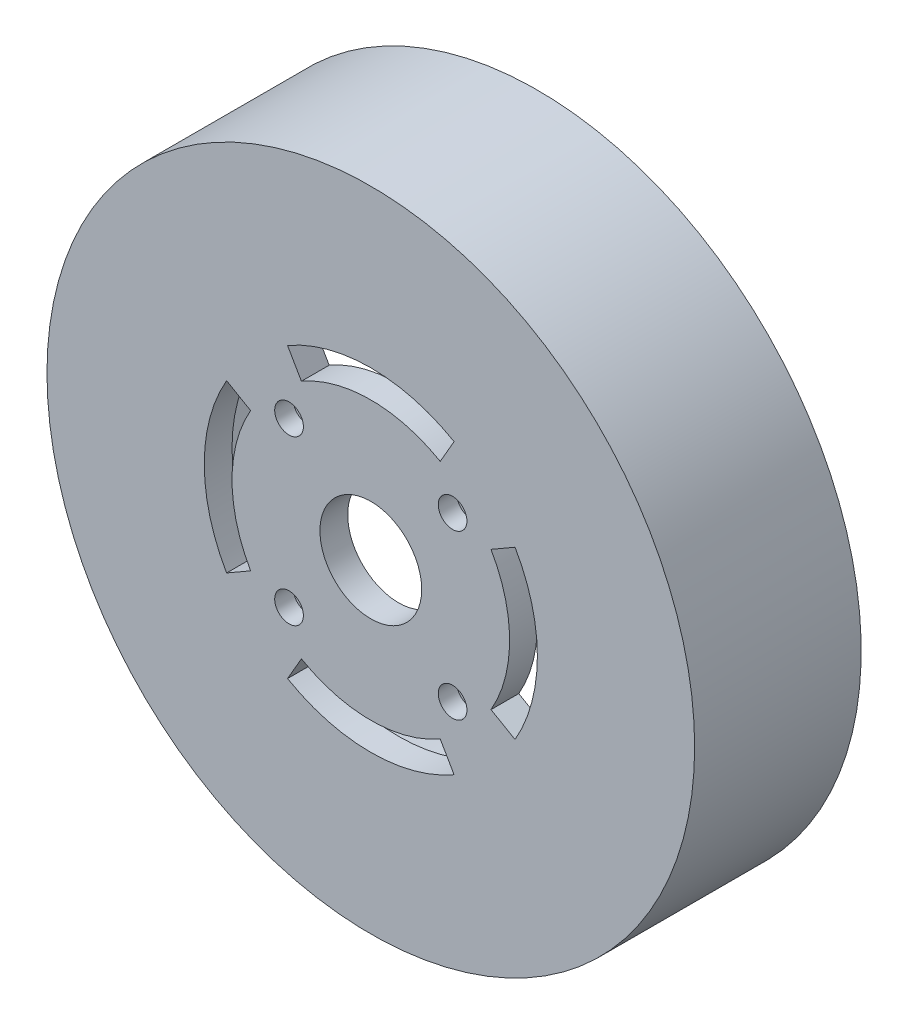
SolidWorks part; units mm, degrees
ref_plane "前视基准面" through (0, 0, 0) normal (0, 0, 1) x (1, 0, 0)
ref_plane "上视基准面" through (0, 0, 0) normal (0, 1, 0) x (1, 0, 0)
ref_plane "右视基准面" through (0, 0, 0) normal (1, 0, 0) x (0, 0, -1)
other "Configuration Table"
sketch "草图2" plane through (0, 0, 0) normal (0, 0, 1) x (1, 0, 0)
  circle A0 centre (0, 0) radius 35
  circle A1 centre (0, 0) radius 5.5
  dimension "D1" = 70
  dimension "D2" = 11
extrude "凸台-拉伸1" add sketch "草图2" along normal blind 5
sketch "草图3" plane through (0, 0, 0) normal (0, 0, -1) x (-1, 0, 0)
  circle A0 centre (0, 0) radius 30.1
  circle A1 centre (0, 0) radius 35
  dimension "D1" = 60.2
extrude "凸台-拉伸2" add sketch "草图3" along normal blind 15
sketch "草图4" plane through (0, 0, -15) normal (0, 0, -1) x (-1, 0, 0)
  line L0 (0, 0) -> (0, 32.5)
  line L1 (0, 0) -> (32.5, 0)
  line L2 (0, 0) -> (0, -32.5)
  line L3 (0, 0) -> (-32.5, 0)
  circle A0 centre (0, 32.5) radius 1.55
  circle A1 centre (32.5, 0) radius 1.55
  circle A2 centre (0, -32.5) radius 1.55
  circle A3 centre (-32.5, 0) radius 1.55
  point P9 (0, 0)
  point P17 (0, 0)
  dimension "D2" = 4
  dimension "D1" = 4
extrude "切除-拉伸1" cut sketch "草图4" against normal blind 10 contours A0 | A1 | A2 | A3 region at (1.065, 33.565, -15) region at (-32.5, 1.5062, -15) region at (-1.065, -31.435, -15) region at (34.0062, 0, -15)
sketch "草图9" plane through (0, 0, -15) normal (0, 0, -1) x (-1, 0, 0)
  line L0 (0, 0) -> (0, 32.5) construction
  line L1 (0, 0) -> (-21.2839, 21.2839) construction
  circle A0 centre (0, 0) radius 30.1 construction
  arc A1 (-22.0133, 20.5286) -> (-20.5286, 22.0133) centre (-21.2839, 21.2839) cw
  arc A2 (20.5286, 22.0133) -> (22.0133, 20.5286) centre (21.2839, 21.2839) cw
  arc A3 (22.0133, -20.5286) -> (20.5286, -22.0133) centre (21.2839, -21.2839) cw
  arc A4 (-20.5286, -22.0133) -> (-22.0133, -20.5286) centre (-21.2839, -21.2839) cw
  arc A5 (-20.5286, 22.0133) -> (-22.0133, 20.5286) centre (0, 0) ccw
  arc A6 (-22.0133, -20.5286) -> (-20.5286, -22.0133) centre (0, 0) ccw
  arc A7 (20.5286, -22.0133) -> (22.0133, -20.5286) centre (0, 0) ccw
  arc A8 (22.0133, 20.5286) -> (20.5286, 22.0133) centre (0, 0) ccw
  point P21 (0, 0)
  dimension "D2" = 1.05
  dimension "D1" = 45
  dimension "D3" = 4
extrude "切除-拉伸5" cut sketch "草图9" against normal up to surface (15 mm away) up to face at (5.5, 0, 0)
fillet "圆角1" radius 1 4 edges at (0, -30.1, -15) (-30.1, 0, -15) (0, 30.1, -15) (30.1, 0, -15)
sketch "草图10" plane through (0, 0, 5) normal (0, 0, 1) x (1, 0, 0)
  circle A0 centre (0, 0) radius 35
extrude "切除-拉伸6" cut sketch "草图10" against normal blind 2
sketch "草图11" plane through (0, 0, 0) normal (0, 0, -1) x (-1, 0, 0)
  line L0 (0, 0) -> (0, 32.5) construction
  line L1 (0, 0) -> (32.5, 0) construction
  line L2 (12.9904, 7.5) -> (15.5885, 9)
  line L3 (-7.5, 12.9904) -> (-9, 15.5885)
  line L4 (7.5, 12.9904) -> (9, 15.5885)
  line L5 (12.9904, -7.5) -> (15.5885, -9)
  line L6 (0, 0) -> (0, -32.5) construction
  line L7 (7.5, -12.9904) -> (9, -15.5885)
  line L8 (-7.5, -12.9904) -> (-9, -15.5885)
  line L9 (0, 0) -> (-32.5, 0) construction
  line L10 (-12.9904, -7.5) -> (-15.5885, -9)
  line L11 (-12.9904, 7.5) -> (-15.5885, 9)
  arc A1 (7.5, 12.9904) -> (-7.5, 12.9904) centre (0, 0) ccw
  arc A2 (9, 15.5885) -> (-9, 15.5885) centre (0, 0) ccw
  arc A3 (12.9904, -7.5) -> (12.9904, 7.5) centre (0, 0) ccw
  arc A4 (15.5885, -9) -> (15.5885, 9) centre (0, 0) ccw
  arc A5 (-7.5, -12.9904) -> (7.5, -12.9904) centre (0, 0) ccw
  arc A6 (-9, -15.5885) -> (9, -15.5885) centre (0, 0) ccw
  arc A7 (-12.9904, 7.5) -> (-12.9904, -7.5) centre (0, 0) ccw
  arc A8 (-15.5885, 9) -> (-15.5885, -9) centre (0, 0) ccw
  point P26 (0, 0)
  dimension "D4" = 30
  dimension "D1" = 4
extrude "切除-拉伸7" cut sketch "草图11" against normal blind 10
sketch "Sketch5" plane through (0, 0, 3) normal (0, 0, 1) x (1, 0, 0)
  line L0 (0, 0) -> (0, 35) construction
  line L1 (0, 0) -> (-24.7487, 24.7487) construction
  line L2 (0, 0) -> (24.7487, 24.7487) construction
  line L3 (0, 0) -> (-8.8388, 8.8388) construction
  line L4 (0, 0) -> (8.8388, -8.8388) construction
  line L5 (0, 0) -> (8.8388, 8.8388) construction
  line L6 (0, 0) -> (-8.8388, -8.8388) construction
  line L7 (8.8388, 8.8388) -> (8.8388, -8.8388) construction
  line L8 (8.8388, -8.8388) -> (-8.8388, -8.8388) construction
  line L9 (-8.8388, -8.8388) -> (-8.8388, 8.8388) construction
  line L10 (-8.8388, 8.8388) -> (8.8388, 8.8388) construction
  circle A0 centre (0, 0) radius 35 construction
  circle A1 centre (8.8388, 8.8388) radius 1.55
  circle A3 centre (8.8388, -8.8388) radius 1.55
  circle A4 centre (-8.8388, -8.8388) radius 1.55
  circle A5 centre (-8.8388, 8.8388) radius 1.55
  point P23 (0, 0)
  dimension "D2" = 3.1
  dimension "D3" = 4
  dimension "D1" = 45
extrude "Cut-Extrude2" cut sketch "Sketch5" against normal blind 2
